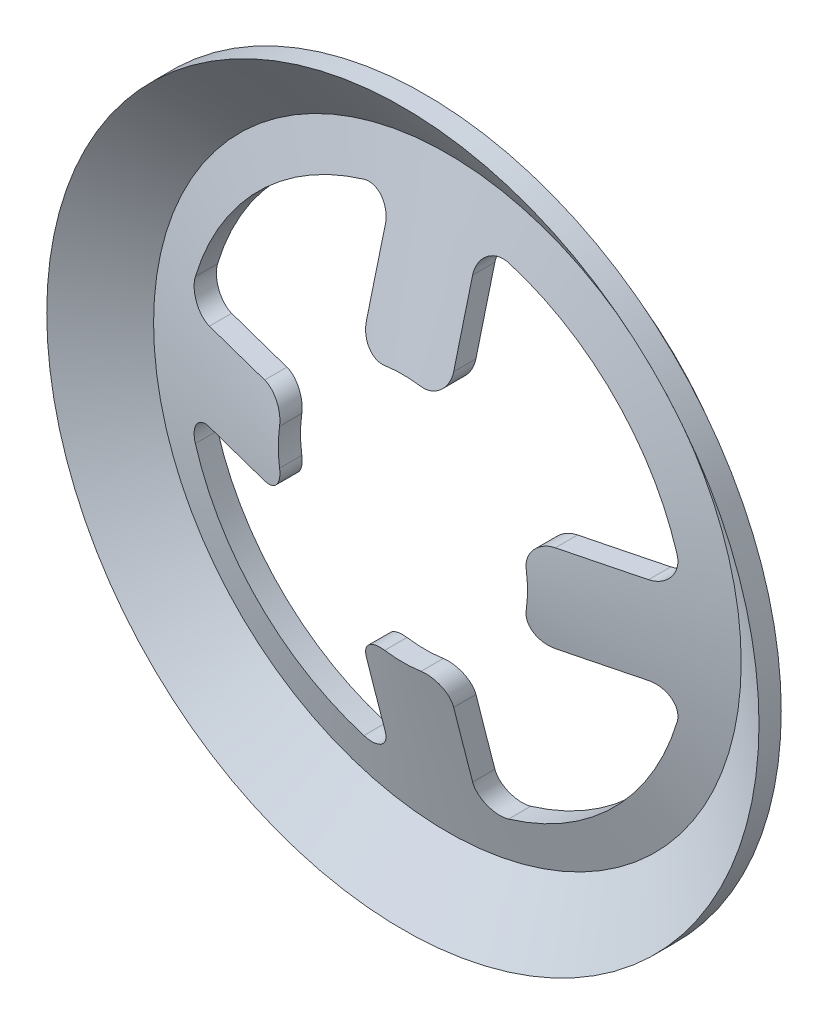
SolidWorks part; units mm, degrees
ref_plane "Front" through (0, 0, 0) normal (0, 0, 1) x (1, 0, 0)
ref_plane "Top" through (0, 0, 0) normal (0, 1, 0) x (1, 0, 0)
ref_plane "Right" through (0, 0, 0) normal (1, 0, 0) x (0, 0, -1)
sketch "Sketch1" plane through (0, 0, 0) normal (0, 0, 1) x (1, 0, 0)
  line L1 (0, 4) -> (0, 3.3) construction
  line L2 (0, 3.3) -> (0, 2.35) construction
  line L3 (0, 2.35) -> (0, 1.4) construction
  line L4 (0, 0) -> (-4, 0) construction
  line L5 (0, 0) -> (-2.8284, 2.8284) construction
  line L6 (-2.8284, 2.8284) -> (2.8284, 2.8284) construction
  line L7 (0, 0) -> (2.8284, 2.8284) construction
  line L8 (0, 0) -> (4, 0) construction
  line L12 (0, 0) -> (-2.7821, 0.4906) construction
  line L13 (0, 0) -> (-0.4906, 2.7821) construction
  circle A0 centre (0, 0) radius 4 construction
  circle A1 centre (0, 0) radius 1.4 construction
  circle A2 centre (0, 0) radius 3.3 construction
  circle A3 centre (0, 0) radius 2.825 construction
  point P3 (0, 2.8284)
  point P5 (-1.4, 0)
  point P12 (0, 2.825)
  point P24 (0, 0)
  point P27 (0, 0)
  dimension "Ring OD" = 8
  dimension "Ring ID" = 2.8
  dimension "D4" = 10
  dimension "D5" = 0.7
  dimension "Degree" = 90
sketch "Sketch4" plane through (0, 0, 0) normal (1, 0, 0) x (0, 0, -1)
  line L0 (-0.125, 0) -> (0.125, 0) construction
  point P4 (0, 0)
  dimension "Ring Thickness" = 0.25
sketch "Sketch2" plane through (0, 0, 0) normal (1, 0, 0) x (0, 0, -1)
  line L0 (-0.375, 0) -> (0.375, 0) construction
  line L1 (-0.375, 0) -> (-0.375, 4) construction
  line L2 (0.375, 0) -> (0.375, 4) construction
  line L3 (-0.375, 4) -> (0.375, 4) construction
  line L4 (-0.375, 3.3) -> (0.375, 3.3) construction
  line L5 (-0.375, 2.35) -> (0.375, 2.35) construction
  line L6 (-0.375, 1.4) -> (0.375, 1.4) construction
  line L7 (-0.375, 4) -> (0.125, 3.3)
  line L8 (0.125, 3.3) -> (-0.375, 1.4)
  line L9 (-0.375, 4) -> (-0.125, 4)
  line L10 (-0.375, 1.4) -> (-0.125, 1.4)
  line L11 (-0.125, 4) -> (0.375, 3.3)
  line L12 (0.375, 3.3) -> (-0.125, 1.4)
  dimension "D1" = 0.75
  dimension "D2" = 0.25
revolve "Revolve1" add sketch "Sketch2" angle 360 about L0
sketch "Sketch3" plane through (0, 0, 0) normal (0, 0, 1) x (1, 0, 0)
  line L0 (-0.4906, 2.7821) -> (-0.4906, 0.4906)
  line L1 (-2.7821, 0.4906) -> (-0.4906, 0.4906)
  line L3 (0, 0) -> (-2.7821, 0.4906) construction
  circle A0 centre (0, 0) radius 2.825 construction
  arc A1 (-0.4906, 2.7821) -> (-2.7821, 0.4906) centre (0, 0) ccw
  dimension "D1" = 10
extrude "Cut-Extrude1" cut sketch "Sketch3" against normal through all both and the other way through all
fillet "Fillet1" radius 0.25 4 edges at (-1.3112, 0.4906, 0.25) (-0.4906, 1.3112, 0.25) (-2.7821, 0.4906, -0.125) (-0.4906, 2.7821, -0.125)
pattern_circular "CirPattern1" count 4 over 360 about axis through (0, 0, 0.375) along (0, 0, 1) of "Cut-Extrude1", "Fillet1"
ref_axis "Axis1" through (0, 0, -0.4125) along (0, 0, 1)
equation "\"RingID\"=5.94514"
equation "\"D1@Sketch2\" = \"Ring Thickness@Sketch4\" * 3"
equation "\"D2@Sketch2\"=\"Ring Thickness@Sketch4\""
equation "\"D1@Sketch3\" = \"D4@Sketch1\""
equation "\"D1@Fillet1\" = \"Ring Thickness@Sketch4\""
